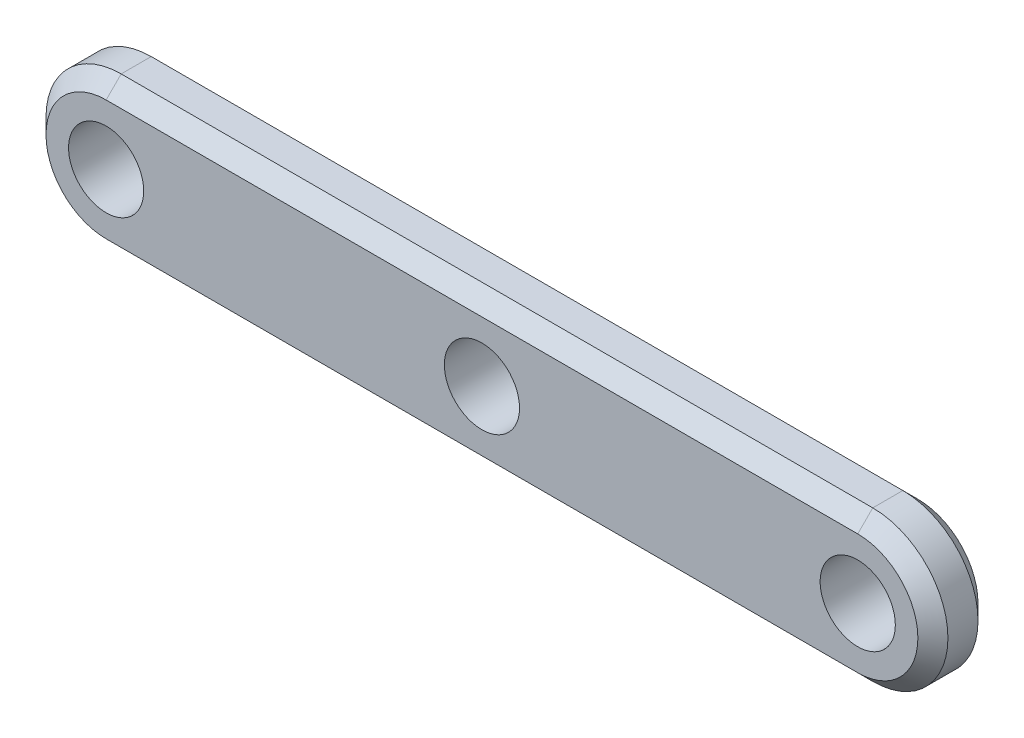
SolidWorks part; units mm, degrees
material "Copper"
ref_plane "Front Plane" through (0, 0, 0) normal (0, 0, 1) x (1, 0, 0)
ref_plane "Top Plane" through (0, 0, 0) normal (0, 1, 0) x (1, 0, 0)
ref_plane "Right Plane" through (0, 0, 0) normal (1, 0, 0) x (0, 0, -1)
sketch "Sketch1" plane through (0, 0, 0) normal (0, 0, 1) x (1, 0, 0)
  line L0 (0, 5) -> (50, 5)
  line L1 (50, -5) -> (0, -5)
  line L2 (0, 0) -> (50, 0) construction
  circle A0 centre (0, 0) radius 5
  circle A1 centre (50, 0) radius 5
  circle A2 centre (50, 0) radius 2.5
  circle A3 centre (0, 0) radius 2.5
  circle A4 centre (25, 0) radius 2.5
  dimension "D1" = 10
  dimension "D2" = 50
  dimension "D3" = 5
extrude "Boss-Extrude1" add sketch "Sketch1" along normal blind 4 contours A1 L0 A0 L1 | A1 A2 | A0 A3 | L2 A0 L1 A1 A4 region at (25, 2.6442, 0) region at (3.4355, 3.4355, 0) region at (53.4355, 3.4355, 0) region at (25, -2.6442, 0)
chamfer "Chamfer1" distance 1 angle 45 8 edges at (25, -5, 0) (-5, 0, 0) (55, 0, 0) (25, 5, 0) (25, -5, 4) (-5, 0, 4) (55, 0, 4) (25, 5, 4)
